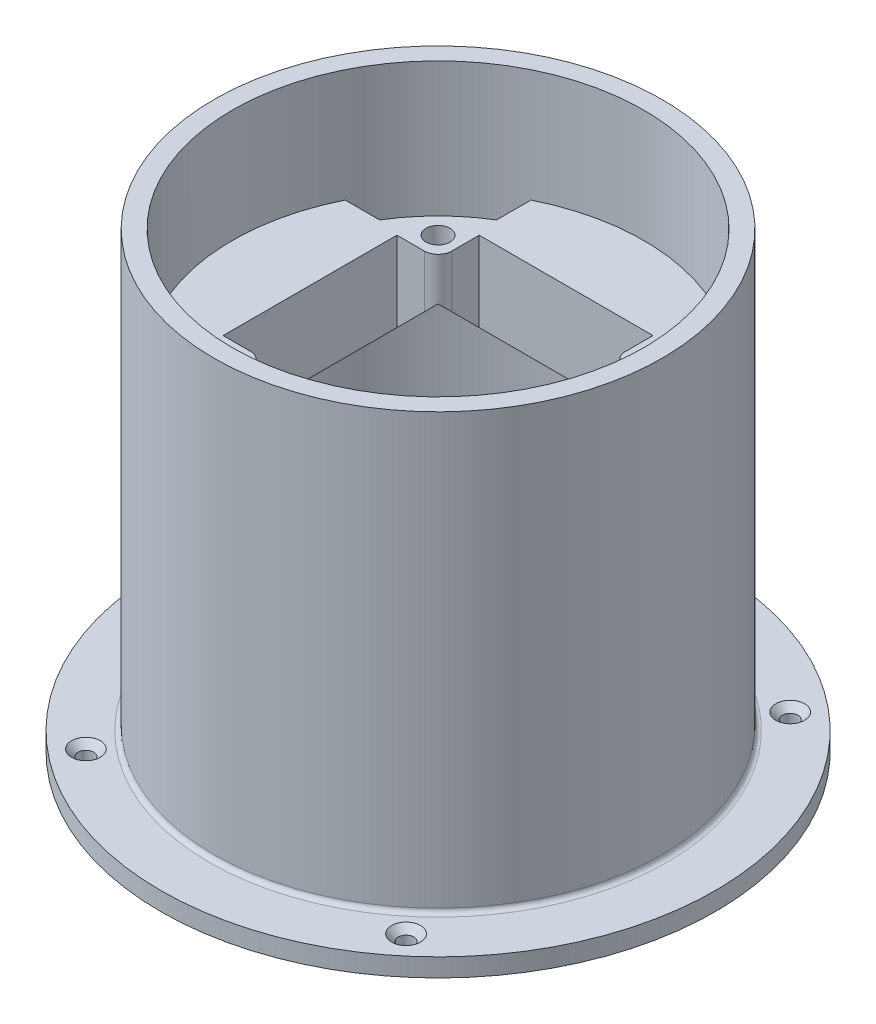
SolidWorks part; units mm, degrees
ref_plane "Front Plane" through (0, 0, 0) normal (0, 0, 1) x (1, 0, 0)
ref_plane "Top Plane" through (0, 0, 0) normal (0, 1, 0) x (1, 0, 0)
ref_plane "Right Plane" through (0, 0, 0) normal (1, 0, 0) x (0, 0, -1)
sketch "Sketch1" plane through (0, 0, 0) normal (0, 1, 0) x (1, 0, 0)
  line L0 (0, 0) -> (0, -34.7391) construction
  line L1 (0, 0) -> (65.335, 0) construction
  circle A0 centre (0, 0) radius 60.625
  circle A1 centre (0, 0) radius 45
  dimension "D1" = 121.25
  dimension "D2" = 90
extrude "Boss-Extrude4" add sketch "Sketch1" along normal blind 4
sketch "Sketch5" plane through (0, 4, 0) normal (0, 1, 0) x (1, 0, 0)
  circle A0 centre (0, 0) radius 45 construction
  circle A1 centre (0, 0) radius 45
  circle A2 centre (0, 0) radius 49
  dimension "D1" = 4
extrude "Boss-Extrude7" add sketch "Sketch5" along normal blind 95
sketch "Sketch8" plane through (0, 0, 0) normal (1, 0, 0) x (0, 0, -1)
  line L0 (-47.5, 74.3) -> (-47.5, 66.3)
  line L1 (-47.5, 66.3) -> (-18.5, 66.3)
  line L2 (-18.5, 66.3) -> (-18.5, 74.3)
  line L3 (-18.5, 74.3) -> (-47.5, 74.3)
  line L4 (-45, 99) -> (-45, 0)
  line L5 (-18.5, 66.3) -> (-45, 39.8)
  line L11 (0, 0) -> (0, 100.9418) construction
  line L12 (18.5, 66.3) -> (45, 39.8)
  line L13 (45, 99) -> (-45, 99) construction
  line L14 (47.5, 74.3) -> (47.5, 66.3)
  line L15 (47.5, 66.3) -> (18.5, 66.3)
  line L16 (18.5, 66.3) -> (18.5, 74.3)
  line L17 (18.5, 74.3) -> (47.5, 74.3)
  line L18 (45, 99) -> (45, 0)
  dimension "D1" = 2.5
  dimension "D5" = 8
  dimension "D6" = 29
  dimension "D7" = 45
  dimension "D9" = 24.7
sketch "Sketch13" plane through (0, 4, 0) normal (0, 1, 0) x (1, 0, 0)
  line L1 (-35, -42) -> (35, -42) construction
  line L2 (-35, -42) -> (-35, 42) construction
  line L3 (-35, 42) -> (35, 42) construction
  line L4 (35, -42) -> (35, 42) construction
  line L5 (-35, -42) -> (35, 42)
  line L6 (-35, 42) -> (35, -42)
  point P0 (0, 0)
  dimension "D1" = 84
  dimension "D2" = 70
sketch "Sketch14" plane through (0, 4, 0) normal (0, 1, 0) x (1, 0, 0)
  point P0 (-35, 42)
  point P3 (35, 42)
  point P6 (35, -42)
  point P9 (-35, -42)
hole_wizard "CSK for M3 Countersunk Flat Head Screw1" positions "Sketch14" profile "Sketch15" countersink size "M3" standard "DIN"
sketch "Sketch15" plane through (-35, 4, -42) normal (1, 0, 0) x (0, 0, 1)
  line L0 (0, 0) -> (0, 5.0215)
  line L1 (0, 5.0215) -> (1.7, 4)
  line L2 (1.7, 4) -> (1.7, 1.45)
  line L3 (1.7, 1.45) -> (3.15, 0)
  line L5 (3.15, 0) -> (0, 0)
  line L6 (-1.7, 1.45) -> (-3.15, 0) construction
  line L10 (0, 5.0215) -> (-1.7, 4) construction
  line L11 (0, -6.35) -> (0, 107.95) construction
  dimension "Hole Dia." = 3.4
  dimension "Hole Depth" = 4
  dimension "Near C'Sink Dia." = 6.3
  dimension "Near C'Sink Angle" = 90
  dimension "Drill Angle" = 118
fillet "Fillet1" radius 1 1 edges at (0, 4, 49)
extrude "Boss-Extrude8" add sketch "Sketch8" along normal mid plane 40 contours L3 L4 L1 L2 | L5 L1 L4 | L18 L17 L16 L15 | L18 L15 L12 | L17 L18 L15 L14 | L2 L3 L0 L1 region at (0, 70.3, 31.75) region at (0, 57.4667, 36.1667) region at (0, 57.4667, -36.1667) region at (0, 70.3, -31.75) region at (0, 70.3, -46.25)
pattern_circular "CirPattern1" count 2 every 90 about axis through (0, 99, 0) along (0, 1, 0) of "Boss-Extrude8"
sketch "Sketch17" plane through (0, 74.3, 0) normal (0, 1, 0) x (1, 0, 0)
  line L0 (-28, 28) -> (28, -28) construction
  line L5 (-23.5, 23.5) -> (23.5, 23.5) construction
  line L6 (-23.5, 23.5) -> (-23.5, -23.5) construction
  line L7 (-23.5, -23.5) -> (23.5, -23.5) construction
  line L8 (23.5, 23.5) -> (23.5, -23.5) construction
  line L9 (-23.5, -23.5) -> (23.5, 23.5) construction
  line L16 (-19, -19) -> (-19, -28)
  line L17 (-19, -28) -> (19, -28)
  line L19 (19, 19) -> (28, 19)
  line L20 (19, -19) -> (19, -28)
  line L21 (-28, 19) -> (-19, 19)
  line L22 (-28, -19) -> (-19, -19)
  line L23 (19, -19) -> (28, -19)
  line L24 (-19, 28) -> (-19, 19)
  line L25 (19, 28) -> (19, 19)
  line L27 (28, 19) -> (28, -19)
  line L28 (-28, 19) -> (-28, -19)
  line L29 (-19, 28) -> (19, 28)
  circle A0 centre (0, 0) radius 38.4
  circle A1 centre (-23.5, 23.5) radius 2.625
  circle A2 centre (23.5, 23.5) radius 2.625
  circle A3 centre (23.5, -23.5) radius 2.625
  circle A4 centre (-23.5, -23.5) radius 2.625
  point P17 (0, 0)
  point P18 (0, 0)
  dimension "D1" = 76.8
  dimension "D3" = 5.25
  dimension "D2" = 47
  dimension "D5" = 38
extrude "Boss-Extrude11" add sketch "Sketch17" against normal blind 8 contours L22 L16 L17 L20 L23 L27 L19 L25 L29 L24 L21 L28 | A0
extrude "Cut-Extrude2" cut sketch "Sketch17<5>" against normal through all contours L28 L22 L16 L17 L20 L23 L27 L19 L25 L29 L24 L21 | A1 | A2 | A3 | A4
sketch "Sketch17<5>" plane through (0, 74.3, 0) normal (0, 1, 0) x (1, 0, 0) same geometry as "Sketch17"
fillet "Fillet2" radius 3 4 edges at (19, 70.05, 19) (19, 70.05, -19) (-19, 70.05, 19) (-19, 70.05, -19)
sketch "Sketch18" plane through (0, 99, 0) normal (0, 1, 0) x (1, 0, 0)
  circle A0 centre (0, 0) radius 49
  circle A1 centre (0, 0) radius 57.8875
extrude "Cut-Extrude3" cut sketch "Sketch18" against normal blind 80
